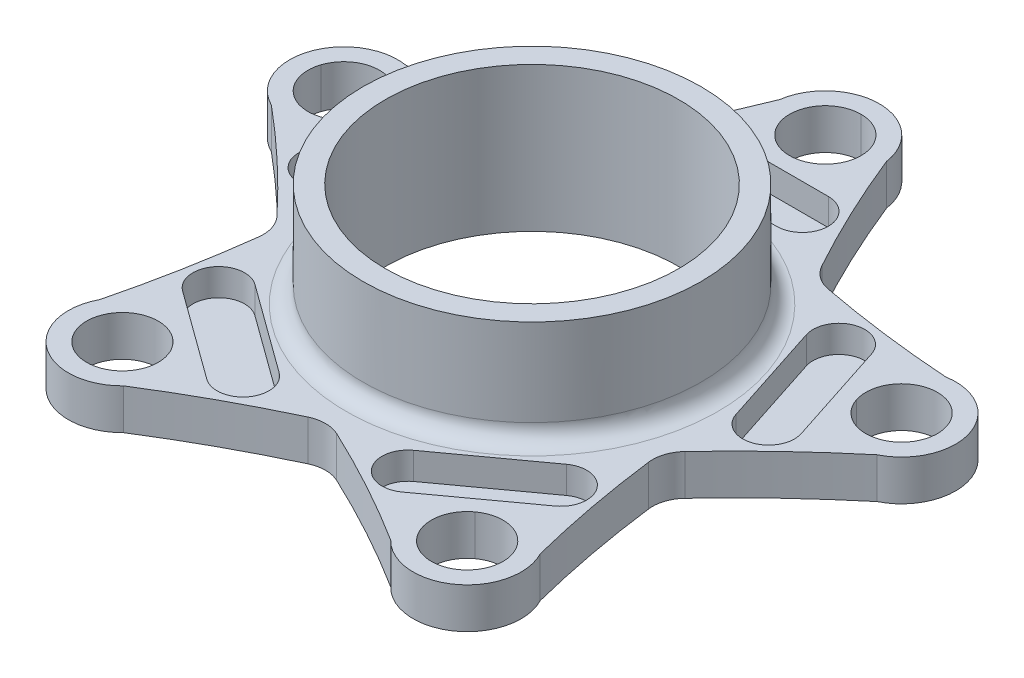
SolidWorks part; units mm, degrees
note: '?' marks a value the reader was unsure of.
ref_plane "Front Plane" through (0, 0, 0) normal (0, 0, 1) x (1, 0, 0)
ref_plane "Top Plane" through (0, 0, 0) normal (0, 1, 0) x (1, 0, 0)
ref_plane "Right Plane" through (0, 0, 0) normal (1, 0, 0) x (0, 0, -1)
sketch "Sketch1" plane through (0, 0, 0) normal (0, 1, 0) x (1, 0, 0)
  circle A0 centre (0, 0) radius 31.75
  dimension "D1" = 63.5
extrude "CenterCircleExtrude" add sketch "Sketch1" along normal blind 19.558 contours A0
sketch "Sketch2" plane through (0, 0, 0) normal (0, -1, 0) x (1, 0, 0)
  circle A0 centre (0, 0) radius 80.01
  dimension "D1" = 160.02
extrude "BaseExpand" add sketch "Sketch2" along normal blind 7.62
fillet "Fillet15" radius 3.175 1 edges at (0, 0, 31.75)
sketch "Sketch3" plane through (0, 19.558, 0) normal (0, 1, 0) x (1, 0, 0)
  circle A0 centre (0, 0) radius 27.559
  dimension "D1" = 55.118
extrude "CenterCut" cut sketch "Sketch3" against normal blind 27.178 contours A0
sketch "Sketch4" plane through (0, 0, 0) normal (0, 1, 0) x (1, 0, 0)
  line L0 (-52.4203, 17.0324) -> (0, 55.118) construction
  line L1 (-26.2102, 36.0752) -> (-18.6622, 25.6863) construction
  circle A0 centre (0, 55.118) radius 6.731
  circle A1 centre (52.4203, 17.0324) radius 6.731
  circle A2 centre (32.3975, -44.5914) radius 6.731
  circle A3 centre (-32.3975, -44.5914) radius 6.731
  circle A4 centre (-52.4203, 17.0324) radius 6.731
  circle A5 centre (0, 0) radius 31.75 construction
  point P14 (0, 0)
  dimension "D1" = 13.462
  dimension "D2" = 55.118
  dimension "D3" = 5
extrude "OuterCircleCut" cut sketch "Sketch4" against normal blind 7.62
sketch "Sketch8" plane through (0, 0, 0) normal (0, 1, 0) x (1, 0, 0)
  line L0 (-52.4203, 17.0324) -> (0, 55.118) construction
  line L1 (-26.2102, 36.0752) -> (-18.6622, 25.6863) construction
  line L2 (26.2102, 36.0752) -> (18.6622, 25.6863) construction
  line L3 (42.4089, -13.7795) -> (30.196, -9.8113) construction
  line L4 (0, -44.5914) -> (0, -31.75) construction
  line L5 (-42.4089, -13.7795) -> (-30.196, -9.8113) construction
  line L6 (0, -14.9479) -> (0, 14.9479) construction
  line L8 (0, 0) -> (10.16, 55.118) construction
  line L9 (10.16, 55.118) -> (-10.16, 55.118) construction
  circle A0 centre (-52.4203, 17.0324) radius 10.16
  circle A1 centre (0, 55.118) radius 10.16
  circle A2 centre (52.4203, 17.0324) radius 10.16
  circle A3 centre (32.3975, -44.5914) radius 10.16
  circle A4 centre (-32.3975, -44.5914) radius 10.16
  circle A5 centre (0, 0) radius 31.75 construction
  arc A6 (22.4362, 30.8807) -> (8.4002, 60.8331) centre (204.9622, 134.6791) cw
  arc A7 (-22.4362, 30.8807) -> (-8.4002, 60.8331) centre (-204.9622, 134.6791) ccw
  arc A8 (22.4362, 30.8807) -> (55.2599, 26.7875) centre (64.7506, 236.5488) ccw
  arc A9 (36.3025, -11.7954) -> (60.4515, 10.8094) centre (191.4243, -153.3125) cw
  arc A10 (36.3025, -11.7954) -> (42.5527, -44.2774) centre (244.9803, 11.5161) ccw
  arc A11 (0, -38.1707) -> (28.9609, -54.1525) centre (-86.6555, -229.4315) cw
  arc A12 (0, -38.1707) -> (-28.9609, -54.1525) centre (86.6555, -229.4315) ccw
  arc A13 (-36.3025, -11.7954) -> (-42.5527, -44.2774) centre (-244.9803, 11.5161) cw
  arc A14 (-36.3025, -11.7954) -> (-60.4515, 10.8094) centre (-191.4243, -153.3125) ccw
  arc A15 (-22.4362, 30.8807) -> (-55.2599, 26.7875) centre (-64.7506, 236.5488) cw
  point P14 (0, 0)
  point P27 (0, 0)
  point P63 (0, 0)
  point P72 (0, 0)
  dimension "D1" = 5
  dimension "D3" = 5
  dimension "D2" = 5
extrude "StarfishCut" cut sketch "Sketch8" against normal blind 7.62
sketch "Sketch14" plane through (0, 0, 0) normal (0, 1, 0) x (1, 0, 0)
  line L4 (-32.1414, -26.7407) -> (-15.4997, -38.8316) construction
  line L20 (-29.2815, -22.8043) -> (-12.6397, -34.8953)
  line L23 (-35.0013, -30.6771) -> (-18.3596, -42.768)
  line L24 (-35.3641, 22.305) -> (-41.7207, 2.7414) construction
  line L25 (-30.7367, 20.8014) -> (-37.0933, 1.2379)
  line L26 (-39.9916, 23.8085) -> (-46.3482, 4.245)
  line L27 (10.2852, 40.5259) -> (-10.2852, 40.5259) construction
  line L28 (10.2852, 35.6603) -> (-10.2852, 35.6603)
  line L29 (10.2852, 45.3915) -> (-10.2852, 45.3915)
  line L30 (41.7207, 2.7414) -> (35.3641, 22.305) construction
  line L31 (37.0933, 1.2379) -> (30.7367, 20.8014)
  line L32 (46.3482, 4.245) -> (39.9916, 23.8085)
  line L33 (15.4997, -38.8316) -> (32.1414, -26.7407) construction
  line L34 (12.6397, -34.8953) -> (29.2815, -22.8043)
  line L35 (18.3596, -42.768) -> (35.0013, -30.6771)
  arc A74 (-29.2815, -22.8043) -> (-35.0013, -30.6771) centre (-32.1414, -26.7407) ccw
  arc A75 (-18.3596, -42.768) -> (-12.6397, -34.8953) centre (-15.4997, -38.8316) ccw
  arc A76 (-30.7367, 20.8014) -> (-39.9916, 23.8085) centre (-35.3641, 22.305) ccw
  arc A77 (-46.3482, 4.245) -> (-37.0933, 1.2379) centre (-41.7207, 2.7414) ccw
  arc A78 (10.2852, 35.6603) -> (10.2852, 45.3915) centre (10.2852, 40.5259) ccw
  arc A79 (-10.2852, 45.3915) -> (-10.2852, 35.6603) centre (-10.2852, 40.5259) ccw
  arc A80 (37.0933, 1.2379) -> (46.3482, 4.245) centre (41.7207, 2.7414) ccw
  arc A81 (39.9916, 23.8085) -> (30.7367, 20.8014) centre (35.3641, 22.305) ccw
  arc A82 (12.6397, -34.8953) -> (18.3596, -42.768) centre (15.4997, -38.8316) ccw
  arc A83 (35.0013, -30.6771) -> (29.2815, -22.8043) centre (32.1414, -26.7407) ccw
  point P5 (-23.8205, -32.7862)
  point P10 (0, 40.5259)
  point P11 (0, 0)
  point P15 (-38.5424, 12.5232)
  point P22 (0, 40.5259)
  point P29 (38.5424, 12.5232)
  point P34 (0, 0)
  point P37 (23.8205, -32.7862)
  point P42 (0, 0)
  point P51 (0.0346, -0.0647)
  point P61 (0, 0)
  point P93 (0, 0)
  point P97 (0, 0)
  dimension "D1" = 5
extrude "Batman Cut" cut sketch "Sketch14" against normal blind 5.08
ref_axis "Axis1" through (0, -7.62, 0) along (0, 1, 0)?
fillet "Fillet12" radius 6.35 5 edges at (-36.3025, -3.81, 11.7954) (0, -3.81, 38.1707) (36.3025, -3.81, 11.7954) (22.4362, -3.81, -30.8807) (-22.4362, -3.81, -30.8807)
ref_plane "Plane1" through (0, 0, 0) normal (-0.309, 0, 0.9511) x (0.9511, 0, 0.309)
ref_plane "Plane2" through (0, 0, 0) normal (-0.809, 0, -0.5878) x (-0.5878, 0, 0.809)
ref_plane "Plane3" through (0, 0, 0) normal (-0.809, 0, 0.5878) x (0.5878, 0, 0.809)
ref_plane "Plane4" through (0, 0, 0) normal (0.309, 0, 0.9511) x (0.9511, 0, -0.309)
split line "Split Line1"
split line "Split Line2"
split line "Split Line3"
split line "Split Line4"
split line "Split Line5"
